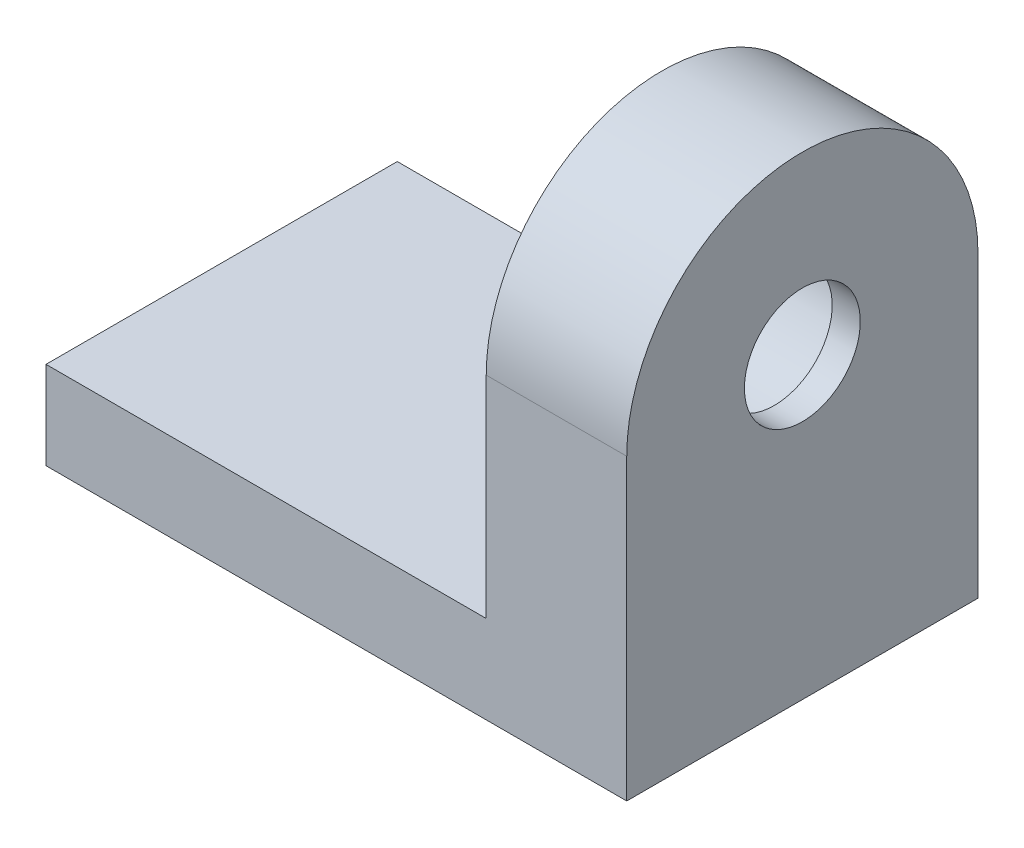
SolidWorks part; units mm, degrees
ref_plane "Front Plane" through (0, 0, 0) normal (0, 0, 1) x (1, 0, 0)
ref_plane "Top Plane" through (0, 0, 0) normal (0, 1, 0) x (1, 0, 0)
ref_plane "Right Plane" through (0, 0, 0) normal (1, 0, 0) x (0, 0, -1)
sketch "Sketch1" plane through (0, 0, 0) normal (1, 0, 0) x (0, 0, -1)
  line L0 (-10, 0) -> (-10, -17)
  line L1 (10, 0) -> (10, -17)
  line L2 (10, -17) -> (-10, -17)
  arc A0 (10, 0) -> (-10, 0) centre (0, 0) ccw
  dimension "D1" = 20
  dimension "D2" = 17
extrude "Boss-Extrude1" add sketch "Sketch1" along normal blind 8
hole_wizard "CBORE for M6 Hex Socket Head Cap Screw1" positions "Sketch3" profile "Sketch4" counterbore size "M6" standard "ISO"
sketch "Sketch3" plane through (0, 0, 0) normal (-1, 0, 0) x (0, 0, 1)
  point P0 (0, 0)
sketch "Sketch4" plane through (0, 0, 0) normal (0, 1, 0) x (0, 0, 1)
  line L0 (0, 0) -> (0, 31.9828)
  line L1 (0, 31.9828) -> (3.3, 30)
  line L2 (3.3, 30) -> (3.3, 6.4)
  line L3 (3.3, 6.4) -> (5.5, 6.4)
  line L4 (5.5, 6.4) -> (5.5, 0)
  line L5 (5.5, 0) -> (0, 0)
  line L10 (0, 31.9828) -> (-3.3, 30) construction
  line L11 (0, -6.35) -> (0, 107.95) construction
  dimension "Hole Dia." = 6.6
  dimension "Hole Depth" = 30
  dimension "C'Bore Dia." = 11
  dimension "C'Bore Depth" = 6.4
  dimension "Drill Angle" = 118
sketch "Sketch5" plane through (0, 0, 0) normal (-1, 0, 0) x (0, 0, 1)
  line L0 (10, 0) -> (10, -17) construction
  line L1 (-10, -17) -> (10, -17)
  line L2 (-10, -17) -> (-10, -12)
  line L3 (-10, -12) -> (10, -12)
  line L4 (10, -17) -> (10, -12)
  dimension "D1" = 5
extrude "Boss-Extrude2" add sketch "Sketch5" along normal blind 25.065
sketch "Sketch6" plane through (0, -12, 0) normal (0, 1, 0) x (1, 0, 0)
  line L0 (-12.5325, 10) -> (-12.5325, -10) construction
  line L1 (-25.065, 10) -> (0, 10) construction
  line L2 (-25.065, -10) -> (0, -10) construction
  line L3 (-12.5325, 6) -> (-25.065, 6) construction
  line L4 (-25.065, -10) -> (-25.065, 10) construction
  line L5 (-12.5325, -6) -> (-25.065, -6) construction
  point P6 (-12.5325, 6)
  point P10 (-12.5325, -6)
  dimension "D1" = 4
  dimension "D2" = 4
hole_wizard "CSK for M2 Countersunk Flat Head Screw1" [suppressed] positions "Sketch6" profile "Sketch7" countersink size "M2" standard "ISO"
sketch "Sketch7" plane through (-5, -15, 6) normal (1, 0, 0) x (0, 0, 1)
  line L0 (0, 0) -> (0, 30.721)
  line L1 (0, 30.721) -> (1.2, 30)
  line L2 (1.2, 30) -> (1.2, 1)
  line L3 (1.2, 1) -> (2.2, 0)
  line L5 (2.2, 0) -> (0, 0)
  line L6 (-1.2, 1) -> (-2.2, 0) construction
  line L10 (0, 30.721) -> (-1.2, 30) construction
  line L11 (0, -6.35) -> (0, 107.95) construction
  dimension "Hole Dia." = 2.4
  dimension "Hole Depth" = 30
  dimension "Near C'Sink Dia." = 4.4
  dimension "Near C'Sink Angle" = 90
  dimension "Drill Angle" = 118
sketch "Sketch8" plane through (-25.065, 0, 0) normal (-1, 0, 0) x (0, 0, 1)
  line L0 (-10, -14.5) -> (10, -14.5) construction
  line L1 (-10, -12) -> (-10, -17) construction
  line L2 (10, -17) -> (10, -12) construction
  circle A0 centre (6, -14.5) radius 1.5
  circle A1 centre (-6, -14.5) radius 1.5
  dimension "D4" = 3
  dimension "D5" = 3
  dimension "D1" = 12
  dimension "D2" = 4
  dimension "D3" = 4
extrude "Cut-Extrude1" cut sketch "Sketch8" against normal blind 5
thread "Thread1" pitch 0.5 method cut profile "Thread Profile1" start angle 0, offset 0, length 10, pitch 0.5, diameter 3
ref_plane "Plane1" through (-25.065, -14.5, 4.5) normal (0, -1, 0) x (0, 0, -1)
sketch "Thread Profile1" plane through (-25.065, -14.5, 4.5) normal (0, -1, 0) x (0, 0, -1)
  line L0 (0, 0) -> (0, 0.5) construction
  line L1 (0, 0) -> (0.2706, 0.1562)
  line L2 (0.2706, 0.1562) -> (0.2706, 0.2187)
  line L3 (0.2706, 0.2187) -> (0, 0.375)
  line L4 (0.2706, 0.1875) -> (0, 0.1875) construction
  line L11 (0, 0) -> (0, 0.375)
  point P2 (0, 0)
  dimension "Pitch" = 0.5
  dimension "Profile_Angle" = 60
  dimension "Profile_Land" = 0.0625
  dimension "Profile_Height" = 0.2706
thread "Thread2" pitch 0.5 method cut profile "Thread Profile2" start angle 0, offset 0, length 10, pitch 0.5, diameter 3
ref_plane "Plane2" through (-25.065, -14.5, -7.5) normal (0, -1, 0) x (0, 0, -1)
sketch "Thread Profile2" plane through (-25.065, -14.5, -7.5) normal (0, -1, 0) x (0, 0, -1)
  line L0 (0, 0) -> (0, 0.5) construction
  line L1 (0, 0) -> (0.2706, 0.1562)
  line L2 (0.2706, 0.1562) -> (0.2706, 0.2187)
  line L3 (0.2706, 0.2187) -> (0, 0.375)
  line L4 (0.2706, 0.1875) -> (0, 0.1875) construction
  line L11 (0, 0) -> (0, 0.375)
  point P2 (0, 0)
  dimension "Pitch" = 0.5
  dimension "Profile_Angle" = 60
  dimension "Profile_Land" = 0.0625
  dimension "Profile_Height" = 0.2706
